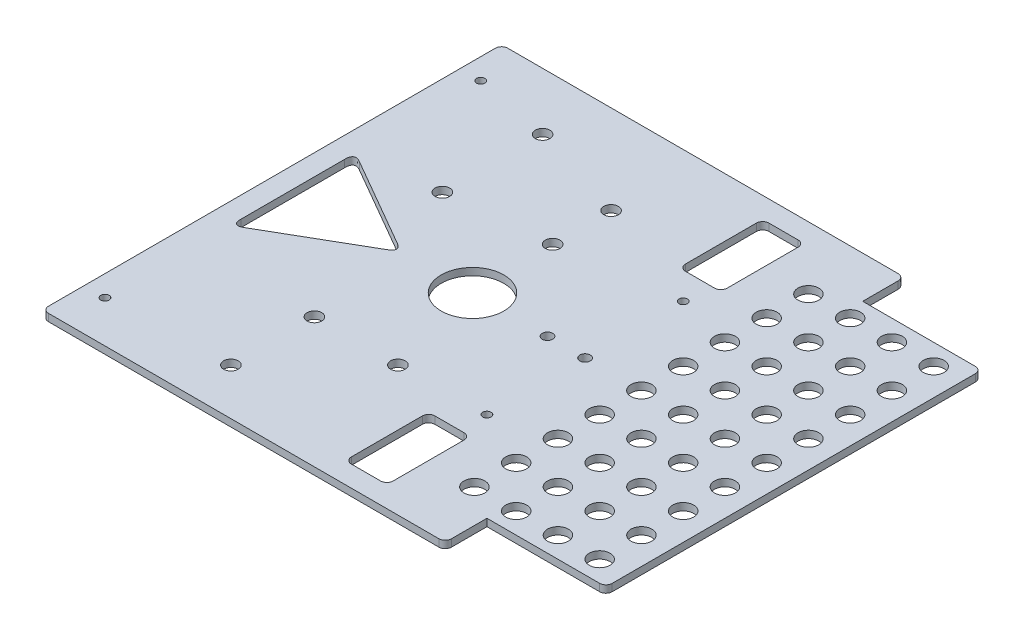
SolidWorks part; units mm, degrees
ref_plane "Front Plane" through (0, 0, 0) normal (0, 0, 1) x (1, 0, 0)
ref_plane "Top Plane" through (0, 0, 0) normal (0, 1, 0) x (1, 0, 0)
ref_plane "Right Plane" through (0, 0, 0) normal (1, 0, 0) x (0, 0, -1)
sketch "Sketch1" plane through (0, 0, 0) normal (0, 1, 0) x (1, 0, 0)
  line L2 (-125, 110) -> (125, 110)
  line L3 (-125, 110) -> (-125, -110)
  line L4 (-125, -110) -> (125, -110)
  line L5 (125, 110) -> (125, -110)
  line L6 (-125, 110) -> (125, -110) construction
  line L7 (-125, -110) -> (125, 110) construction
  point P3 (0, 0)
  dimension "D1" = 250
  dimension "D2" = 220
extrude "the upper chasiss" add sketch "Sketch1" along normal mid plane 3.5 contours L3 L2 L5 L4
sketch "Sketch2" plane through (0, 0, 0) normal (0, 1, 0) x (1, 0, 0)
  line L0 (125, 0) -> (-125, 0) construction
  line L1 (125, 110) -> (125, -110) construction
  line L2 (-125, 110) -> (-125, -110) construction
  circle A0 centre (25, 0) radius 2.5
  circle A1 centre (7, 0) radius 2.5
  dimension "D1" = 5
  dimension "D2" = 5
  dimension "D3" = 18
  dimension "D4" = 100
extrude "Battary" cut sketch "Sketch2" along normal up to surface and the other way up to surface up to face at (0, 1.75, 0) other way up to face at (0, -1.75, 0)
sketch "Sketch3" plane through (0, 0, 0) normal (0, 1, 0) x (1, 0, 0)
  line L1 (-56.8984, -47.7601) -> (-16.8984, -47.7601) construction
  line L2 (-56.8984, -47.7601) -> (-56.8984, -87.7601) construction
  circle A0 centre (-56.8984, -47.7601) radius 3.5
  circle A1 centre (-16.8984, -47.7601) radius 3.5
  circle A2 centre (-56.8984, -87.7601) radius 3.5
  dimension "D1" = 7
  dimension "D2" = 7
  dimension "D3" = 7
  dimension "D4" = 40
  dimension "D5" = 40
extrude "power section" cut sketch "Sketch3" against normal up to surface and the other way up to surface up to face at (25, -1.75, -2.5) other way up to face at (25, 1.75, -2.5)
sketch "arduino" plane through (0, 0, 0) normal (0, 1, 0) x (1, 0, 0)
  line L0 (-77.9335, 82.5888) -> (-77.9335, 34.5888) construction
  line L1 (-77.9335, 34.5888) -> (-29.9335, 39.3888) construction
  line L2 (-29.9335, 39.3888) -> (-29.9335, 67.3888) construction
  line L3 (-29.9335, 67.3888) -> (-77.9335, 82.5888) construction
  circle A0 centre (-77.9335, 82.5888) radius 3.5
  circle A1 centre (-77.9335, 34.5888) radius 3.5
  circle A2 centre (-29.9335, 67.3888) radius 3.5
  circle A3 centre (-29.9335, 39.3888) radius 3.5
  dimension "D1" = 7
  dimension "D2" = 7
  dimension "D3" = 7
  dimension "D4" = 7
  dimension "D5" = 48
  dimension "D6" = 28
  dimension "D7" = 48
  dimension "D8" = 15.2
extrude "arduino section" cut sketch "arduino" against normal mid plane 5
sketch "Sketch7" plane through (0, 1.75, 0) normal (0, 1, 0) x (1, 0, 0)
  line L0 (-125, 0) -> (125, 0) construction
  line L1 (-125, 110) -> (-125, -110) construction
  line L2 (125, 110) -> (125, -110) construction
  line L3 (0, 110) -> (0, -110) construction
  line L4 (-125, 110) -> (125, 110) construction
  line L5 (-125, -110) -> (125, -110) construction
  line L6 (-115, -90) -> (-115, 0) construction
  line L7 (-115, 90) -> (-115, 0) construction
  line L8 (-115, 90) -> (125, 90) construction
  line L9 (25, 90) -> (25, -110) construction
  circle A2 centre (-115, -90) radius 2
  circle A3 centre (-115, 90) radius 2
  circle A8 centre (25, 47) radius 2
  circle A9 centre (25, 0) radius 2.5 construction
  circle A10 centre (25, -47) radius 2
  dimension "D1" = 4
  dimension "D2" = 4
  dimension "D6" = 4
  dimension "D3" = 20
  dimension "D4" = 10
  dimension "D5" = 140
  dimension "D7" = 47
extrude "link nails" cut sketch "Sketch7" against normal mid plane 10
sketch "Sketch9" plane through (0, 1.75, 0) normal (0, 1, 0) x (1, 0, 0)
  line L0 (125, 0) -> (-125, 0) construction
  line L1 (125, 110) -> (125, -110) construction
  line L2 (-125, 110) -> (-125, -110) construction
  line L3 (10.0665, -60) -> (30.0665, -100) construction
  line L4 (10.0665, 100) -> (30.0665, 100)
  line L5 (10.0665, 100) -> (10.0665, 60)
  line L6 (10.0665, 60) -> (30.0665, 60)
  line L7 (30.0665, 100) -> (30.0665, 60)
  line L8 (10.0665, 100) -> (30.0665, 60) construction
  line L9 (10.0665, 60) -> (30.0665, 100) construction
  line L10 (10.0665, -100) -> (30.0665, -60) construction
  line L11 (30.0665, -100) -> (30.0665, -60)
  line L12 (10.0665, -60) -> (30.0665, -60)
  line L13 (10.0665, -100) -> (10.0665, -60)
  line L14 (10.0665, -100) -> (30.0665, -100)
  circle A0 centre (-29.9335, 39.3888) radius 3.5 construction
  circle A1 centre (25, 0) radius 2.5 construction
  point P6 (126.2109, 0)
  dimension "D3" = 40
  dimension "D1" = 20
  dimension "D2" = 40
  dimension "D4" = 60
extrude "rect cut" cut sketch "Sketch9" against normal mid plane 10
sketch "Sketch10" plane through (0, 1.75, 0) normal (0, 1, 0) x (1, 0, 0)
  line L0 (-125, 0) -> (125, 0) construction
  line L1 (-125, 110) -> (-125, -110) construction
  line L2 (125, 110) -> (125, -110) construction
  line L3 (25, -2.5) -> (7, -2.5) construction
  line L4 (16, -2.5) -> (16, 110) construction
  line L5 (-125, 110) -> (125, 110) construction
  circle A0 centre (-28.9235, 0) radius 15
  circle A1 centre (25, 0) radius 2.5 construction
  circle A2 centre (7, 0) radius 2.5 construction
  dimension "D2" = 30
  dimension "D1" = 44.9235
extrude "circ cut" cut sketch "Sketch10" against normal mid plane 10
fillet "Fillet5" radius 3 8 edges at (10.0665, 0, -60) (30.0665, 0, -60) (10.0665, 0, -100) (30.0665, 0, -100) (30.0665, 0, 100) (10.0665, 0, 100) (10.0665, 0, 60) (30.0665, 0, 60)
sketch "Sketch11" plane through (0, 0, 0) normal (0, 1, 0) x (1, 0, 0)
  line L6 (-125, 110) -> (125, 110) construction
  line L9 (125, 110) -> (125, -110) construction
  line L10 (-115, -90) -> (197.2842, -90) construction
  circle A2 centre (112, 80) radius 5
  dimension "D1" = 30
  dimension "D2" = 10
  dimension "D3" = 13
extrude "Cut-Extrude1" cut sketch "Sketch11" against normal mid plane 10
pattern_linear "LPattern1" count 9 spacing 20 along (0, 0, 1) count 4 spacing 20 along (-1, 0, 0) of "Cut-Extrude1"
sketch "Sketch13" plane through (0, 0, 0) normal (0, 1, 0) x (1, 0, 0)
  line L0 (-115, 90) -> (-115, -90) construction
  line L1 (-125, 0) -> (125, 0) construction
  line L2 (-125, 110) -> (-125, -110) construction
  line L3 (125, 110) -> (125, -110) construction
  line L4 (-115, 30) -> (-63.0385, 0)
  line L5 (-63.0385, 0) -> (-115, -30)
  line L6 (-115, -30) -> (-115, 30)
  dimension "D1" = 60
extrude "Cut-Extrude2" cut sketch "Sketch13" against normal mid plane 10
fillet "Fillet6" radius 3 3 edges at (-115, 0, 30) (-63.0385, 0, 0) (-115, 0, -30) curvature continuous yes
sketch "Sketch16" plane through (0, 0, 0) normal (0, 1, 0) x (1, 0, 0)
  line L0 (125, 0) -> (-125, 0) construction
  line L1 (125, 110) -> (125, -110) construction
  line L2 (-125, 110) -> (-125, -110) construction
  line L3 (125, 90) -> (125, -90)
  line L4 (125, -90) -> (68, -90)
  line L5 (68, -90) -> (68, -110)
  line L6 (-125, -110) -> (125, -110) construction
  line L7 (68, 90) -> (68, 110)
  line L8 (125, 90) -> (68, 90)
  dimension "D1" = 90
  dimension "D2" = 57
extrude "Cut-Extrude4" cut sketch "Sketch16" against normal through all both and the other way through all flip side to cut
fillet "Fillet7" radius 3 6 edges at (-125, 0, 110) (68, 0, 110) (125, 0, 90) (125, 0, -90) (68, 0, -110) (-125, 0, -110)
equation "\"carWidth\"= 22cm'the car full width"
equation "\"carLong\"= 32cm"
equation "\"D2@Sketch1\"=\"carWidth\""
equation "\"D1@Sketch1\"=250mm"
equation "\"chasissTheikness\"= 0.35cm"
equation "\"D1@the upper chasiss\"=\"chasissTheikness\" "
equation "\"battaryMargin\"= 1.8cm'the width between the two battary nails"
equation "\"battaryNailsDiam\"= 5mm'battary Nails Diameters"
equation "\"D1@Sketch2\"=\"battaryNailsDiam\""
equation "\"D2@Sketch2\"=\"battaryNailsDiam\""
equation "\"D3@Sketch2\"=\"battaryMargin\""
equation "\"powerWidht\"= 40mm"
equation "\"powerNailDiam\"= 7mm"
equation "\"D1@Sketch3\"=\"powerNailDiam\""
equation "\"D2@Sketch3\"=\"powerNailDiam\""
equation "\"D3@Sketch3\"=\"powerNailDiam\""
equation "\"D4@Sketch3\"=\"powerWidht\""
equation "\"D5@Sketch3\"=\"powerWidht\""
equation "\"arduinoTopWidth\"= 4.8cm'the width between nails"
equation "\"arduinoBottomWidth\"= 2.8cm'the width between nails"
equation "\"arduinoNailsDiam\"= 7mm'the nail diameter"
equation "\"D1@arduino\" = \"arduinoNailsDiam\""
equation "\"D2@arduino\" = \"arduinoNailsDiam\""
equation "\"D3@arduino\" = \"arduinoNailsDiam\""
equation "\"D4@arduino\" = \"arduinoNailsDiam\""
equation "\"D5@arduino\" = \"arduinoTopWidth\""
equation "\"D6@arduino\" = \"arduinoBottomWidth\""
equation "\"D7@arduino\" = \"arduinoTopWidth\""
equation "\"arduinoTobBottomShift\"= 15.2mm"
equation "\"D8@arduino\" = \"arduinoTobBottomShift\""
equation "\"chasissNailsDiam\"= 0.4cm"
equation "\"D2@Sketch7\"=\"chasissNailsDiam\""
equation "\"D1@Sketch7\"=\"chasissNailsDiam\""
equation "\"10ةة\"=12.1958"
equation "\"D6@Sketch7\"=\"chasissNailsDiam\""
